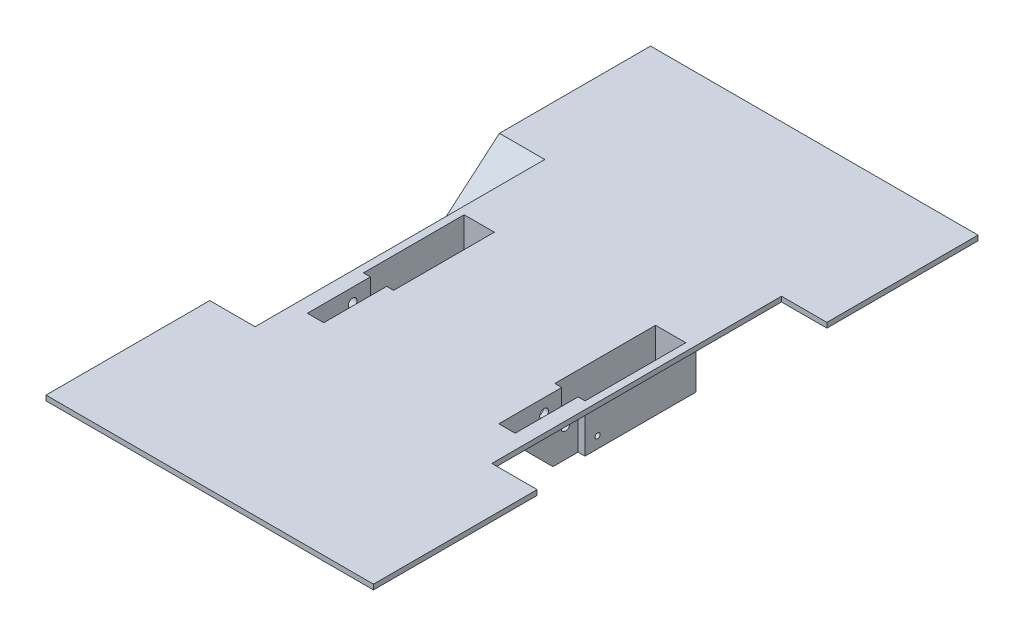
SolidWorks part; units mm, degrees
ref_plane "Front Plane" through (0, 0, 0) normal (0, 0, 1) x (1, 0, 0)
ref_plane "Top Plane" through (0, 0, 0) normal (0, 1, 0) x (1, 0, 0)
ref_plane "Right Plane" through (0, 0, 0) normal (1, 0, 0) x (0, 0, -1)
sketch "Sketch1" plane through (0, 0, 0) normal (0, 1, 0) x (1, 0, 0)
  line L1 (-50, -50) -> (50, -50)
  line L2 (-50, -50) -> (-50, 50)
  line L3 (-50, 50) -> (50, 50)
  line L4 (50, -50) -> (50, 50)
  line L5 (-50, -50) -> (50, 50) construction
  line L6 (-50, 50) -> (50, -50) construction
  point P0 (0, 0)
  dimension "D1" = 100
  dimension "D2" = 100
extrude "Boss-Extrude1" add sketch "Sketch1" along normal blind 2
sketch "Sketch2" plane through (0, 2, 0) normal (0, 1, 0) x (1, 0, 0)
  line L0 (50, -50) -> (50, 50) construction
  line L1 (32, 25) -> (44, 25)
  line L2 (32, 25) -> (32, -25)
  line L3 (32, -25) -> (44, -25)
  line L4 (44, 25) -> (44, -25)
  point P6 (44, 0)
  dimension "D1" = 12
  dimension "D2" = 6
  dimension "D3" = 50
extrude "Cut-Extrude1" cut sketch "Sketch2" against normal up to next
sketch "Sketch3" plane through (0, 0, 0) normal (0, -1, 0) x (1, 0, 0)
  line L0 (38, 25) -> (38, -25) construction
  line L1 (32, 25) -> (34.75, 25)
  line L2 (32, 25) -> (32, 15)
  line L3 (32, 15) -> (34.75, 15)
  line L4 (34.75, 25) -> (34.75, 15)
  line L5 (32, 25) -> (44, 25) construction
  line L6 (44, -25) -> (32, -25) construction
  line L7 (41.25, 25) -> (41.25, 15)
  line L8 (44, 15) -> (41.25, 15)
  line L9 (44, 25) -> (44, 15)
  line L10 (44, 25) -> (41.25, 25)
  dimension "D1" = 6.5
  dimension "D2" = 10
extrude "Boss-Extrude2" add sketch "Sketch3" against normal up to vertex (2 mm away) up to point (32, 2, 25)
sketch "Sketch4" plane through (0, 0, 0) normal (0, -1, 0) x (1, 0, 0)
  line L21 (46, 17) -> (43.25, 17)
  line L22 (46, -27) -> (46, 17)
  line L23 (30, -27) -> (46, -27)
  line L24 (30, 17) -> (30, -27)
  line L25 (32.75, 17) -> (30, 17)
  line L26 (32.75, 27) -> (32.75, 17)
  line L27 (43.25, 27) -> (32.75, 27)
  line L28 (43.25, 17) -> (43.25, 27)
  line L29 (46, 17) -> (43.25, 17)
  line L30 (46, -27) -> (46, 17)
  line L31 (30, -27) -> (46, -27)
  line L32 (30, 17) -> (30, -27)
  line L33 (32.75, 17) -> (30, 17)
  line L34 (32.75, 27) -> (32.75, 17)
  line L35 (43.25, 27) -> (32.75, 27)
  line L36 (43.25, 17) -> (43.25, 27)
  line L45 (44, 15) -> (41.25, 15)
  line L46 (44, -25) -> (44, 15)
  line L47 (32, -25) -> (44, -25)
  line L48 (32, 15) -> (32, -25)
  line L49 (34.75, 15) -> (32, 15)
  line L50 (34.75, 25) -> (34.75, 15)
  line L51 (41.25, 25) -> (34.75, 25)
  line L52 (41.25, 15) -> (41.25, 25)
  line L53 (44, 15) -> (41.25, 15)
  line L54 (44, -25) -> (44, 15)
  line L55 (32, -25) -> (44, -25)
  line L56 (32, 15) -> (32, -25)
  line L57 (34.75, 15) -> (32, 15)
  line L58 (34.75, 25) -> (34.75, 15)
  line L59 (41.25, 25) -> (34.75, 25)
  line L60 (41.25, 15) -> (41.25, 25)
  dimension "D1" = 2
  dimension "D2" = 0
extrude "Boss-Extrude3" add sketch "Sketch4" along normal blind 15
ref_plane "Plane1" through (38, 0, 0) normal (-1, 0, 0) x (0, 0, 1)
sketch "Sketch5" plane through (38, 0, 0) normal (-1, 0, 0) x (0, 0, 1)
  line L0 (-50, 2) -> (50, 2) construction
  line L1 (27, -15) -> (17, -15) construction
  circle A0 centre (22, -3.5) radius 1.75
  circle A1 centre (12, -10.5) radius 1
  point P7 (22, -15)
  dimension "D1" = 3.5
  dimension "D5" = 2
  dimension "D2" = 5.5
  dimension "D3" = 10
  dimension "D4" = 7
extrude "Cut-Extrude2" cut sketch "Sketch5" against normal through all both and the other way through all
chamfer "Chamfer1" distance 15 angle 45 2 edges at (38, 2, 25) (38, 0, 27)
mirror "Mirror1" about plane through (0, 0, 0) normal (1, 0, 0) of "Cut-Extrude2", "Boss-Extrude2", "Chamfer1", "Boss-Extrude3", "Cut-Extrude1"
sketch "Sketch6" plane through (0, 0, 0) normal (0, -1, 0) x (1, 0, 0)
  line L1 (-50, 50) -> (50, 50)
  line L2 (-50, 50) -> (-50, -50)
  line L3 (-50, -50) -> (50, -50)
  line L4 (50, 50) -> (50, -50)
  line L5 (-65, -120) -> (65, -120)
  line L6 (-65, -120) -> (-65, 120)
  line L7 (-65, 120) -> (65, 120)
  line L8 (65, -120) -> (65, 120)
  line L9 (-65, -120) -> (65, 120) construction
  line L10 (-65, 120) -> (65, -120) construction
  point P6 (0, 0)
  dimension "D1" = 130
  dimension "D2" = 240
extrude "Boss-Extrude4" add sketch "Sketch6" against normal up to vertex (2 mm away) up to point (50, 2, -50)
sketch "Sketch7" plane through (0, 0, 0) normal (0, -1, 0) x (1, 0, 0)
  line L0 (-65, 120) -> (-65, -120) construction
  line L1 (-65, 55) -> (-47, 55)
  line L2 (-65, 55) -> (-65, -60)
  line L3 (-65, -60) -> (-47, -60)
  line L4 (-47, 55) -> (-47, -60)
  line L5 (0, -9.35) -> (0, 9.35) construction
  line L6 (65, 55) -> (47, 55)
  line L7 (65, 55) -> (65, -60)
  line L8 (65, -60) -> (47, -60)
  line L9 (47, 55) -> (47, -60)
  line L10 (-65, -120) -> (65, -120) construction
  dimension "D1" = 18
  dimension "D2" = 115
  dimension "D3" = 60
extrude "Cut-Extrude3" cut sketch "Sketch7" against normal up to next
sketch "Sketch8" plane through (-65, 0, 0) normal (-1, 0, 0) x (0, 0, 1)
  line L0 (55, 2) -> (34.2008, -20)
  line L1 (34.2008, -20) -> (-34.2008, -20)
  line L2 (0, 0) -> (0, -20) construction
  line L3 (-60, 2) -> (-34.2008, -20)
  line L4 (-61.2977, 0.4782) -> (-34.9377, -22)
  line L5 (35.0623, -22) -> (-34.9377, -22)
  line L6 (56.4533, 0.626) -> (35.0623, -22)
  line L7 (-60, 2) -> (-61.2977, 0.4782)
  line L8 (55, 2) -> (56.4533, 0.626)
  line L9 (-60, 2) -> (-60, 0) construction
  point P12 (-51.5535, 0.7403)
  point P13 (-60, 2)
  point P16 (-60, 2.9032)
  dimension "D1" = 20
  dimension "D3" = 70
  dimension "D2" = 2
extrude "Boss-Extrude5" add sketch "Sketch8" against normal up to vertex (18 mm away) up to point (-47, 0, -60)
sketch "Sketch9" plane through (-47, 0, 0) normal (1, 0, 0) x (0, 0, -1)
  line L5 (63.0823, 2) -> (-57.7523, 2)
  line L6 (-35.0623, -22) -> (-57.7523, 2)
  line L7 (-55, 2) -> (-120, 2) construction
  line L8 (-35.0623, -22) -> (34.9377, -22)
  line L9 (34.9377, -22) -> (63.0823, 2)
  line L10 (120, 2) -> (60, 2) construction
  line L11 (60.737, 0) -> (34.9377, -22) construction
  line L12 (-35.0623, -22) -> (-55.8615, 0) construction
  circle A0 centre (-22, -3.5) radius 1.75
  circle A1 centre (-12, -10.5) radius 1
  circle A2 centre (-22, -3.5) radius 1.75 construction
  circle A3 centre (-12, -10.5) radius 1 construction
extrude "Boss-Extrude10" add sketch "Sketch9" along normal up to vertex (1 mm away) up to point (-46, -15, 17)
sketch "Sketch10" plane through (-43.25, 0, 0) normal (-1, 0, 0) x (0, 0, 1)
  line L8 (42, 0) -> (17, 0)
  line L9 (17, 0) -> (17, -15)
  line L10 (17, -15) -> (27, -15)
  line L11 (27, -15) -> (42, 0)
  line L12 (42, 0) -> (17, 0)
  line L13 (17, 0) -> (17, -15)
  line L14 (17, -15) -> (27, -15)
  line L15 (27, -15) -> (42, 0)
  circle A0 centre (22, -3.5) radius 1.75
  circle A1 centre (22, -3.5) radius 1.75 construction
  dimension "D1" = 0
extrude "Boss-Extrude11" add sketch "Sketch10" along normal up to vertex up to point (-46, -22, 35.0623)
